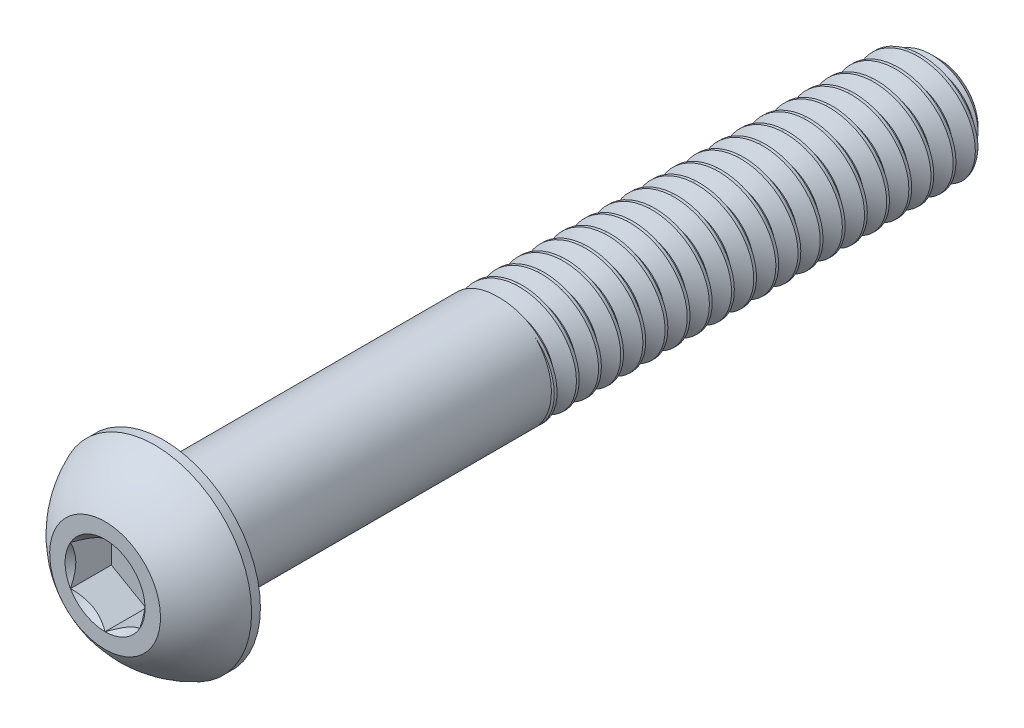
SolidWorks part; units mm, degrees
ref_plane "Front" through (0, 0, 0) normal (0, 0, 1) x (1, 0, 0)
ref_plane "Top" through (0, 0, 0) normal (0, 1, 0) x (1, 0, 0)
ref_plane "Right" through (0, 0, 0) normal (1, 0, 0) x (0, 0, -1)
sketch "Sketch1" plane through (0, 0, 0) normal (1, 0, 0) x (0, 0, -1)
  line L2 (3.3528, 3.175) -> (47.8028, 3.175)
  line L3 (47.8028, 3.175) -> (47.8028, 0)
  line L4 (47.8028, 0) -> (3.3528, 0)
  line L6 (2.8499, 5.5499) -> (3.3528, 5.5499) construction
  line L7 (47.8028, 3.175) -> (47.8028, -3.175) construction
  line L8 (0, 0) -> (3.3528, 0) construction
  line L9 (3.3528, 5.5499) -> (3.3528, -5.5499) construction
  line L11 (3.3528, 3.175) -> (3.3528, 0)
  line L13 (0, 1.9844) -> (0, -1.9844) construction
  line L14 (0, 1.9844) -> (0, 3.175) construction
  arc A3 (0, 3.175) -> (2.8499, 5.5499) centre (5.0603, 0) cw construction
  dimension "D1" = 0.5029
revolve "Revolve1" add sketch "Sketch1" angle 360 mid plane about L4
sketch "Sketch3" plane through (0, 0, -47.8028) normal (0, 0, -1) x (-1, 0, 0)
  circle A0 centre (0, 0) radius 3.175
curve "Helix/Spiral1" pitch 1.27 height 45.72 radius 3.175 centre (0, 0, -47.8028) axis (0, 0, 1) start towards (0, 1, 0)
sketch "Sketch2" plane through (0, 0, 0) normal (1, 0, 0) x (0, 0, -1)
  line L0 (47.8028, 3.175) -> (48.9141, 3.175)
  line L1 (48.9141, 3.175) -> (48.4378, 2.3501)
  line L2 (48.4378, 2.3501) -> (48.279, 2.3501)
  line L3 (48.279, 2.3501) -> (47.8028, 3.175)
  line L4 (48.0409, 2.7626) -> (48.6759, 2.7626) construction
  dimension "D1" = 60
  dimension "D2" = 0.1588
  dimension "D3" = 0.635
chamfer "Chamfer1" distance 0.9525 angle 45 1 edges at (0, 3.175, -47.8028)
sweep "Cut-Sweep1" cut profiles "Sketch2" path "Helix/Spiral1" align with end faces yes
sketch "Sketch7" plane through (0, 0, 0) normal (1, 0, 0) x (0, 0, -1)
  line L6 (2.8499, 5.5499) -> (3.3528, 5.5499) construction
  line L8 (0, 0) -> (3.3528, 0) construction
  line L11 (3.3528, 5.5499) -> (3.3528, -5.5499) construction
  line L12 (2.8499, 5.5499) -> (3.3528, 5.5499)
  line L13 (0, 0) -> (3.3528, 0)
  line L14 (0, 1.9844) -> (0, -1.9844) construction
  line L15 (3.3528, 5.5499) -> (3.3528, 0)
  line L16 (0, 3.175) -> (0, 0)
  arc A2 (2.8499, 5.5499) -> (0, 3.175) centre (5.0603, 0) ccw construction
  arc A3 (2.8499, 5.5499) -> (0, 3.175) centre (5.0603, 0) ccw
revolve "Revolve2" add sketch "Sketch7" angle 360 mid plane about L13
sketch "Sketch5" plane through (0, 0, 0) normal (0, 0, 1) x (1, 0, 0)
  line L1 (1.9844, -1.1457) -> (1.9844, 1.1457)
  line L2 (1.9844, 1.1457) -> (0, 2.2914)
  line L3 (0, 2.2914) -> (-1.9844, 1.1457)
  line L4 (-1.9844, 1.1457) -> (-1.9844, -1.1457)
  line L5 (-1.9844, -1.1457) -> (0, -2.2914)
  line L6 (0, -2.2914) -> (1.9844, -1.1457)
  circle A0 centre (0, 0) radius 1.9844 construction
extrude "Cut-Extrude2" cut sketch "Sketch5" against normal blind 2.347
sketch "Sketch6" plane through (0, 0, 0) normal (0, 0, 1) x (1, 0, 0)
  circle A0 centre (0, 0) radius 2.2914
extrude "Cut-Extrude3" cut sketch "Sketch6" against normal blind 2.347 draft 45
sketch "Sketch9" plane through (0, 0, -3.3528) normal (0, 0, 1) x (1, 0, 0)
  circle A2 centre (0, 0) radius 3.175
extrude "Boss-Extrude2" add sketch "Sketch9" against normal offset from surface (19.05 mm away) 25.4 up to face at (0, 2.2225, -47.8028)
sketch "Sketch10" plane through (0, 0, 0) normal (1, 0, 0) x (0, 0, -1)
  line L0 (47.8028, 3.175) -> (47.8028, -3.175) construction
  point P0 (45.8978, -3.175)
  dimension "D1" = 1.905
equation "\"D3@Helix/Spiral1\" = \"Lg@Sketch1\" + \"D4@Helix/Spiral1\""
equation "\"D2@Sketch2\" = \"D4@Helix/Spiral1\" * .125"
equation "\"D3@Sketch2\" = \"D4@Helix/Spiral1\" * .5"
equation "\"D1@Chamfer1\" = \"D4@Helix/Spiral1\" * .75"
equation "\"D1@Cut-Extrude2\" = \"Head Ht@Sketch1\" * .7"
equation "\"D1@Sketch1\" = \"Head Ht@Sketch1\" * .15"
equation "\"D1@Sketch10\" = \"D4@Helix/Spiral1\" * 1.5"
equation "\"D1@Cut-Extrude3\" = \"D1@Cut-Extrude2\""
